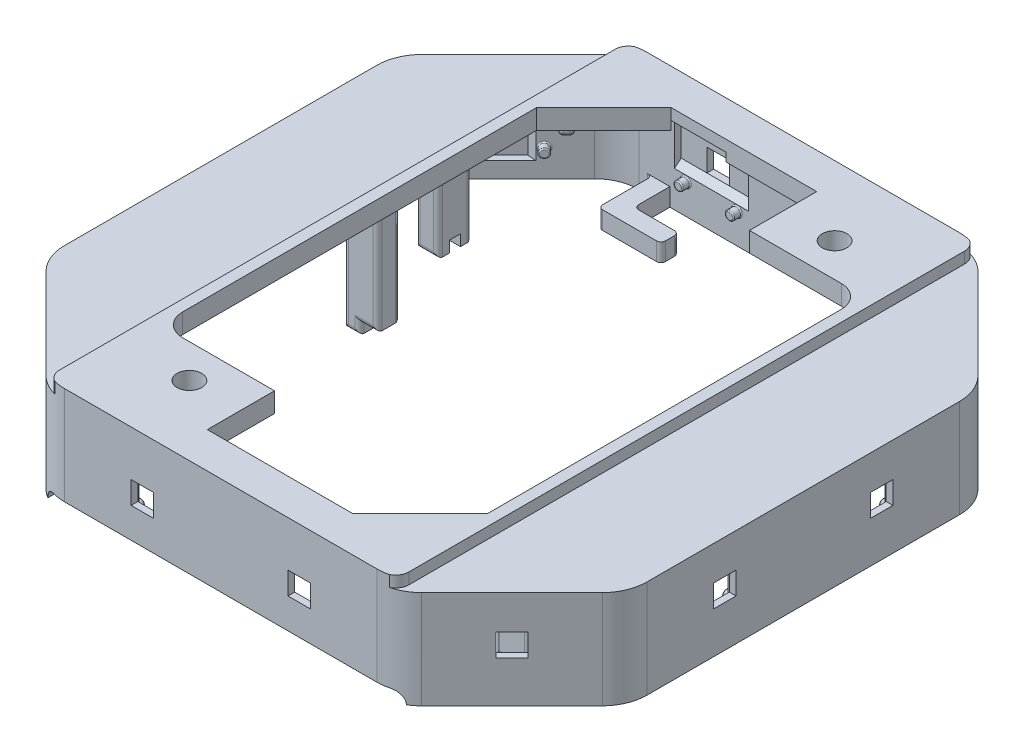
SolidWorks part; units mm, degrees
ref_plane "Front Plane" through (0, 0, 0) normal (0, 0, 1) x (1, 0, 0)
ref_plane "Top Plane" through (0, 0, 0) normal (0, 1, 0) x (1, 0, 0)
ref_plane "Right Plane" through (0, 0, 0) normal (1, 0, 0) x (0, 0, -1)
ref_axis "CenterAxis" through (0, 3.97, 0) along (0, -1, 0)
sketch "Sketch1" plane through (0, 0, 0) normal (0, 1, 0) x (1, 0, 0)
  line L0 (0, 34.664) -> (0, -51.0735) construction
  line L1 (-39, 65) -> (39, 65)
  line L2 (-39, 65) -> (-39, -65)
  line L3 (-39, -65) -> (39, -65)
  line L4 (39, 65) -> (39, -65)
  line L5 (-69.2084, 0) -> (81.5089, 0) construction
  dimension "D1" = 78
  dimension "D2" = 130
extrude "Boss-Extrude1" add sketch "Sketch1" along normal blind 2.5
sketch "Sketch4" plane through (0, 0, 0) normal (0, -1, 0) x (-1, 0, 0)
  line L1 (65, 65) -> (-65, 65)
  line L2 (65, 65) -> (65, -65)
  line L3 (65, -65) -> (-65, -65)
  line L4 (-65, 65) -> (-65, -65)
  line L6 (0, 118.1215) -> (0, -128.1726) construction
  line L7 (153.5171, 0) -> (-213.3352, 0) construction
  dimension "D1" = 130
  dimension "D2" = 130
extrude "Boss-Extrude2" add sketch "Sketch4" along normal blind 1.9
chamfer "Chamfer1" distance 26 angle 45 4 edges at (65, -0.95, 65) (-65, -0.95, 65) (-65, -0.95, -65) (65, -0.95, -65)
sketch "Sketch5" plane through (0, -1.9, 0) normal (0, -1, 0) x (-1, 0, 0)
  line L7 (39, 65) -> (-39, 65) construction
  line L9 (-39, 65) -> (-65, 39) construction
  line L10 (-65, 39) -> (-65, -39) construction
  line L11 (-65, -39) -> (-39, -65) construction
  line L12 (-39, -65) -> (39, -65) construction
  line L13 (39, -65) -> (65, -39) construction
  line L14 (65, -39) -> (65, 39) construction
  line L15 (65, 39) -> (39, 65) construction
  line L16 (39, 65) -> (-39, 65)
  line L17 (-39, 65) -> (-65, 39)
  line L18 (-65, 39) -> (-65, -39)
  line L19 (-65, -39) -> (-39, -65)
  line L20 (-39, -65) -> (39, -65)
  line L21 (39, -65) -> (65, -39)
  line L22 (65, -39) -> (65, 39)
  line L23 (65, 39) -> (39, 65)
  line L24 (37.7574, 62) -> (-37.7574, 62)
  line L25 (-37.7574, 62) -> (-62, 37.7574)
  line L26 (-62, 37.7574) -> (-62, -37.7574)
  line L27 (-62, -37.7574) -> (-37.7574, -62)
  line L28 (-37.7574, -62) -> (37.7574, -62)
  line L29 (37.7574, -62) -> (62, -37.7574)
  line L30 (62, -37.7574) -> (62, 37.7574)
  line L31 (62, 37.7574) -> (37.7574, 62)
  dimension "D1" = 3
extrude "Boss-Extrude3" add sketch "Sketch5" along normal blind 20
sketch "Sketch6" plane through (0, 0, 62) normal (0, 0, -1) x (-1, 0, 0)
  line L0 (0, -73.719) -> (0, 48.5048) construction
  line L1 (-15, -12.65) -> (-20, -12.65)
  line L2 (-15, -12.65) -> (-15, -7.65)
  line L3 (-15, -7.65) -> (-20, -7.65)
  line L4 (-20, -12.65) -> (-20, -7.65)
  line L5 (20, -12.65) -> (15, -12.65)
  line L6 (20, -12.65) -> (20, -7.65)
  line L7 (20, -7.65) -> (15, -7.65)
  line L8 (15, -12.65) -> (15, -7.65)
  line L10 (-37.7574, -1.9) -> (37.7574, -1.9) construction
  dimension "D1" = 5
  dimension "D2" = 5
  dimension "D3" = 5
  dimension "D4" = 5
  dimension "D5" = 30
  dimension "D6" = 5.75
  dimension "D7" = 5.75
extrude "Cut-Extrude3" cut sketch "Sketch6" against normal up to next
sketch "Sketch13" plane through (-49.8787, 0, 49.8787) normal (0.7071, 0, -0.7071) x (-0.7071, 0, -0.7071)
  line L0 (-17.1421, -1.9) -> (17.1421, -1.9) construction
  line L1 (2.5, -12.65) -> (-2.5, -12.65)
  line L2 (2.5, -12.65) -> (2.5, -7.65)
  line L3 (2.5, -7.65) -> (-2.5, -7.65)
  line L4 (-2.5, -12.65) -> (-2.5, -7.65)
  line L5 (0, -31.7169) -> (0, 9.0748) construction
  line L6 (-17.1421, -21.9) -> (-17.1421, -1.9) construction
  line L7 (17.1421, -21.9) -> (17.1421, -1.9) construction
  dimension "D1" = 5
  dimension "D2" = 5
  dimension "D3" = 5.75
extrude "Cut-Extrude6" cut sketch "Sketch13" against normal up to next
sketch "Sketch9" plane through (0, 0, 62) normal (0, 0, -1) x (-1, 0, 0)
  line L0 (39.1927, -10.15) -> (-34.1415, -10.15) construction
  line L4 (20, -18.4) -> (7.35, -18.4)
  line L5 (20, -18.4) -> (20, -1.9)
  line L6 (20, -1.9) -> (7.35, -1.9)
  line L7 (7.35, -18.4) -> (7.35, -1.9)
  line L10 (-20, -18.4) -> (-7.35, -18.4)
  line L11 (-20, -18.4) -> (-20, -1.9)
  line L12 (-20, -1.9) -> (-7.35, -1.9)
  line L13 (-7.35, -18.4) -> (-7.35, -1.9)
  line L18 (-37.7574, -1.9) -> (37.7574, -1.9) construction
  line L19 (20, -12.65) -> (20, -7.65) construction
  line L20 (-20, -7.65) -> (-20, -12.65) construction
  line L21 (20, -7.65) -> (15, -7.65) construction
  line L22 (15, -12.65) -> (20, -12.65) construction
  dimension "D1" = 12.65
  dimension "D2" = 12.65
extrude "Cut-Extrude5" cut sketch "Sketch9" against normal blind 1.5
sketch "Sketch14" plane through (-49.8787, 0, 49.8787) normal (0.7071, 0, -0.7071) x (-0.7071, 0, -0.7071)
  line L0 (-17.1421, -1.9) -> (17.1421, -1.9) construction
  line L1 (2.5, -1.9) -> (-10.15, -1.9)
  line L2 (2.5, -1.9) -> (2.5, -18.4)
  line L3 (2.5, -18.4) -> (-10.15, -18.4)
  line L4 (-10.15, -1.9) -> (-10.15, -18.4)
  line L5 (2.5, -12.65) -> (2.5, -7.65) construction
  line L6 (10.5909, -10.15) -> (-6.85, -10.15) construction
  line L7 (2.5, -7.65) -> (-2.5, -7.65) construction
  line L8 (-2.5, -12.65) -> (2.5, -12.65) construction
  dimension "D1" = 12.65
extrude "Cut-Extrude7" cut sketch "Sketch14" against normal blind 1.5
sketch "Sketch10" plane through (0, 0, 62) normal (0, 0, -1) x (-1, 0, 0)
  line L0 (45.2947, -10.154) -> (11.3128, -10.154) construction
  line L4 (7.35, -18.4) -> (5.35, -18.4)
  line L5 (7.35, -18.4) -> (7.35, -1.9)
  line L6 (7.35, -1.9) -> (5.35, -1.9)
  line L7 (5.35, -18.4) -> (5.35, -1.9)
  line L8 (-7.35, -1.9) -> (7.35, -1.9) construction
  line L9 (-7.35, -18.4) -> (-5.35, -18.4)
  line L10 (-7.35, -18.4) -> (-7.35, -1.9)
  line L11 (-7.35, -1.9) -> (-5.35, -1.9)
  line L12 (-5.35, -18.4) -> (-5.35, -1.9)
  circle A0 centre (22.59, -15.869) radius 1
  circle A1 centre (22.59, -4.439) radius 1
  circle A2 centre (-22.59, -15.869) radius 1
  circle A3 centre (-22.59, -4.439) radius 1
  dimension "D1" = 2
  dimension "D2" = 2
  dimension "D3" = 2
  dimension "D4" = 2
  dimension "D5" = 11.43
  dimension "D6" = 11.43
  dimension "D7" = 8.254
  dimension "D8" = 15.24
  dimension "D9" = 2
  dimension "D10" = 2
  dimension "D11" = 15.24
extrude "Boss-Extrude5" add sketch "Sketch10" along normal blind 1.75
sketch "Sketch15" plane through (-49.8787, 0, 49.8787) normal (0.7071, 0, -0.7071) x (-0.7071, 0, -0.7071)
  line L0 (-17.1421, -1.9) -> (-10.15, -1.9) construction
  line L1 (-10.15, -18.4) -> (-12.15, -18.4)
  line L2 (-10.15, -18.4) -> (-10.15, -1.9)
  line L3 (-10.15, -1.9) -> (-12.15, -1.9)
  line L4 (-12.15, -18.4) -> (-12.15, -1.9)
  line L5 (11.6969, -10.15) -> (-6.9983, -10.15) construction
  line L6 (-2.5, -12.65) -> (2.5, -12.65) construction
  line L7 (2.5, -7.65) -> (-2.5, -7.65) construction
  circle A0 centre (5.09, -15.865) radius 1
  circle A1 centre (5.09, -4.435) radius 1
  dimension "D2" = 2
  dimension "D3" = 2
  dimension "D1" = 2
  dimension "D4" = 15.24
  dimension "D5" = 11.43
extrude "Boss-Extrude9" add sketch "Sketch15" along normal blind 1.75
sketch "Sketch16" plane through (-62, 0, 0) normal (1, 0, 0) x (0, 0, -1)
  line L0 (0, -45.9705) -> (0, 131.7483) construction
  line L1 (20, -12.65) -> (15, -12.65)
  line L2 (20, -12.65) -> (20, -7.65)
  line L3 (20, -7.65) -> (15, -7.65)
  line L4 (15, -12.65) -> (15, -7.65)
  line L5 (-15, -12.65) -> (-20, -12.65)
  line L6 (-15, -12.65) -> (-15, -7.65)
  line L7 (-15, -7.65) -> (-20, -7.65)
  line L8 (-20, -12.65) -> (-20, -7.65)
  line L9 (37.7574, -21.9) -> (37.7574, -1.9) construction
  line L10 (-37.7574, -21.9) -> (-37.7574, -1.9) construction
  line L11 (-37.7574, -1.9) -> (37.7574, -1.9) construction
  dimension "D1" = 30
  dimension "D2" = 5
  dimension "D3" = 5
  dimension "D4" = 5
  dimension "D5" = 5
  dimension "D6" = 5.75
  dimension "D7" = 5.75
extrude "Cut-Extrude8" cut sketch "Sketch16" against normal up to next
sketch "Sketch17" plane through (-62, 0, 0) normal (1, 0, 0) x (0, 0, -1)
  line L0 (20, -12.65) -> (20, -7.65) construction
  line L1 (-15, -18.4) -> (-27.65, -18.4)
  line L2 (-15, -18.4) -> (-15, -1.9)
  line L3 (-15, -1.9) -> (-27.65, -1.9)
  line L4 (-27.65, -18.4) -> (-27.65, -1.9)
  line L5 (20, -18.4) -> (7.35, -18.4)
  line L6 (20, -18.4) -> (20, -1.9)
  line L7 (20, -1.9) -> (7.35, -1.9)
  line L8 (7.35, -18.4) -> (7.35, -1.9)
  line L9 (-37.7574, -1.9) -> (37.7574, -1.9) construction
  line L10 (-15, -12.65) -> (-15, -7.65) construction
  line L11 (27.4384, -10.15) -> (-34.0605, -10.15) construction
  line L12 (15, -12.65) -> (20, -12.65) construction
  line L13 (20, -7.65) -> (15, -7.65) construction
  dimension "D1" = 12.65
  dimension "D2" = 12.65
extrude "Cut-Extrude9" cut sketch "Sketch17" against normal blind 1.5
sketch "Sketch18" plane through (-62, 0, 0) normal (1, 0, 0) x (0, 0, -1)
  line L0 (32.9525, -10.15) -> (-38.3333, -10.15) construction
  line L1 (20, -12.65) -> (15, -12.65) construction
  line L2 (15, -7.65) -> (20, -7.65) construction
  line L3 (7.35, -1.9) -> (7.35, -18.4) construction
  line L4 (-27.65, -1.9) -> (-27.65, -18.4) construction
  line L5 (-15, -1.9) -> (7.35, -1.9) construction
  line L6 (7.35, -18.4) -> (5.35, -18.4)
  line L7 (7.35, -18.4) -> (7.35, -1.9)
  line L8 (7.35, -1.9) -> (5.35, -1.9)
  line L9 (5.35, -18.4) -> (5.35, -1.9)
  line L10 (-37.7574, -1.9) -> (-27.65, -1.9) construction
  line L11 (-27.65, -18.4) -> (-29.65, -18.4)
  line L12 (-27.65, -18.4) -> (-27.65, -1.9)
  line L13 (-27.65, -1.9) -> (-29.65, -1.9)
  line L14 (-29.65, -18.4) -> (-29.65, -1.9)
  circle A0 centre (22.59, -15.865) radius 1
  circle A1 centre (22.59, -4.435) radius 1
  circle A2 centre (-12.41, -15.865) radius 1
  circle A3 centre (-12.41, -4.435) radius 1
  dimension "D3" = 2
  dimension "D4" = 2
  dimension "D5" = 2
  dimension "D6" = 2
  dimension "D1" = 11.43
  dimension "D2" = 11.43
  dimension "D7" = 15.24
  dimension "D8" = 15.24
  dimension "D9" = 2
  dimension "D10" = 2
extrude "Boss-Extrude10" add sketch "Sketch18" along normal blind 1.75
sketch "Sketch19" plane through (49.8787, 0, 49.8787) normal (-0.7071, 0, -0.7071) x (-0.7071, 0, 0.7071)
  line L0 (0, -22.7201) -> (0, -10.1184) construction
  line L3 (17.1421, -21.9) -> (17.1421, -1.9) construction
  line L4 (-17.1421, -21.9) -> (-17.1421, -1.9) construction
  line L5 (-17.1421, -1.9) -> (17.1421, -1.9) construction
  line L6 (2.5, -12.65) -> (-2.5, -12.65)
  line L7 (2.5, -12.65) -> (2.5, -7.65)
  line L8 (2.5, -7.65) -> (-2.5, -7.65)
  line L9 (-2.5, -12.65) -> (-2.5, -7.65)
  dimension "D1" = 5
  dimension "D2" = 5
  dimension "D3" = 5.75
extrude "Cut-Extrude10" cut sketch "Sketch19" against normal up to next
sketch "Sketch20" plane through (49.8787, 0, 49.8787) normal (-0.7071, 0, -0.7071) x (-0.7071, 0, 0.7071)
  line L0 (-17.1421, -1.9) -> (17.1421, -1.9) construction
  line L1 (10.15, -18.4) -> (-2.5, -18.4)
  line L2 (10.15, -18.4) -> (10.15, -1.9)
  line L3 (10.15, -1.9) -> (-2.5, -1.9)
  line L4 (-2.5, -18.4) -> (-2.5, -1.9)
  line L5 (-2.5, -7.65) -> (-2.5, -12.65) construction
  line L6 (13.9228, -10.15) -> (-12.316, -10.15) construction
  line L7 (-2.5, -12.65) -> (2.5, -12.65) construction
  line L8 (2.5, -7.65) -> (-2.5, -7.65) construction
  dimension "D1" = 12.65
extrude "Cut-Extrude11" cut sketch "Sketch20" against normal blind 1.5
sketch "Sketch21" plane through (49.8787, 0, 49.8787) normal (-0.7071, 0, -0.7071) x (-0.7071, 0, 0.7071)
  line L0 (15.0556, -10.15) -> (-12.6108, -10.15) construction
  line L1 (12.15, -18.4) -> (10.15, -18.4)
  line L2 (12.15, -18.4) -> (12.15, -1.9)
  line L3 (12.15, -1.9) -> (10.15, -1.9)
  line L4 (10.15, -18.4) -> (10.15, -1.9)
  line L5 (2.5, -12.65) -> (-2.5, -12.65) construction
  line L6 (-2.5, -7.65) -> (2.5, -7.65) construction
  line L7 (10.15, -1.9) -> (17.1421, -1.9) construction
  circle A0 centre (-5.09, -15.865) radius 1
  circle A1 centre (-5.09, -4.435) radius 1
  dimension "D1" = 2
  dimension "D2" = 2
  dimension "D3" = 2
  dimension "D4" = 15.24
  dimension "D5" = 11.43
extrude "Boss-Extrude11" add sketch "Sketch21" along normal blind 1.75
sketch "Sketch22" plane through (62, 0, 0) normal (-1, 0, 0) x (0, 0, 1)
  line L0 (0, -48.3456) -> (0, 13.9543) construction
  line L1 (20, -12.65) -> (15, -12.65)
  line L2 (20, -12.65) -> (20, -7.65)
  line L3 (20, -7.65) -> (15, -7.65)
  line L4 (15, -12.65) -> (15, -7.65)
  line L5 (-15, -12.65) -> (-20, -12.65)
  line L6 (-15, -12.65) -> (-15, -7.65)
  line L7 (-15, -7.65) -> (-20, -7.65)
  line L8 (-20, -12.65) -> (-20, -7.65)
  line L9 (37.7574, -21.9) -> (37.7574, -1.9) construction
  line L10 (-37.7574, -21.9) -> (-37.7574, -1.9) construction
  line L12 (-37.7574, -1.9) -> (37.7574, -1.9) construction
  dimension "D1" = 5
  dimension "D2" = 5
  dimension "D3" = 5
  dimension "D4" = 5
  dimension "D5" = 5.75
  dimension "D6" = 5.75
  dimension "D7" = 30
extrude "Cut-Extrude12" cut sketch "Sketch22" against normal up to next
sketch "Sketch23" plane through (62, 0, 0) normal (-1, 0, 0) x (0, 0, 1)
  line L1 (27.65, -18.4) -> (15, -18.4)
  line L2 (27.65, -18.4) -> (27.65, -1.9)
  line L3 (27.65, -1.9) -> (15, -1.9)
  line L4 (15, -18.4) -> (15, -1.9)
  line L5 (-7.35, -18.4) -> (-20, -18.4)
  line L6 (-7.35, -18.4) -> (-7.35, -1.9)
  line L7 (-7.35, -1.9) -> (-20, -1.9)
  line L8 (-20, -18.4) -> (-20, -1.9)
  line L10 (-37.7574, -1.9) -> (37.7574, -1.9) construction
  line L11 (30.5276, -10.15) -> (-34.6722, -10.15) construction
  line L12 (20, -7.65) -> (15, -7.65) construction
  line L13 (15, -12.65) -> (20, -12.65) construction
  line L14 (15, -7.65) -> (15, -12.65) construction
  line L15 (-20, -7.65) -> (-20, -12.65) construction
  dimension "D1" = 12.65
  dimension "D2" = 12.65
extrude "Cut-Extrude13" cut sketch "Sketch23" against normal blind 1.5
sketch "Sketch24" plane through (62, 0, 0) normal (-1, 0, 0) x (0, 0, 1)
  line L0 (29.9106, -10.15) -> (-34.7522, -10.15) construction
  line L1 (29.65, -18.4) -> (27.65, -18.4)
  line L2 (29.65, -18.4) -> (29.65, -1.9)
  line L3 (29.65, -1.9) -> (27.65, -1.9)
  line L4 (27.65, -18.4) -> (27.65, -1.9)
  line L5 (-5.35, -18.4) -> (-7.35, -18.4)
  line L6 (-5.35, -18.4) -> (-5.35, -1.9)
  line L7 (-5.35, -1.9) -> (-7.35, -1.9)
  line L8 (-7.35, -18.4) -> (-7.35, -1.9)
  line L9 (20, -12.65) -> (15, -12.65) construction
  line L10 (15, -7.65) -> (20, -7.65) construction
  line L11 (-7.35, -1.9) -> (15, -1.9) construction
  line L12 (27.65, -1.9) -> (37.7574, -1.9) construction
  circle A0 centre (12.41, -15.865) radius 1
  circle A1 centre (12.41, -4.435) radius 1
  circle A2 centre (-22.59, -15.865) radius 1
  circle A3 centre (-22.59, -4.435) radius 1
  dimension "D1" = 2
  dimension "D2" = 2
  dimension "D3" = 2
  dimension "D4" = 2
  dimension "D5" = 2
  dimension "D6" = 2
  dimension "D7" = 15.24
  dimension "D8" = 15.24
  dimension "D9" = 11.43
  dimension "D10" = 11.43
extrude "Boss-Extrude12" add sketch "Sketch24" along normal blind 1.75
sketch "Sketch27" plane through (0, -1.9, 0) normal (0, -1, 0) x (-1, 0, 0)
  line L0 (-25.75, 57) -> (-9.25, 57)
  line L3 (37.7574, 62) -> (-37.7574, 62) construction
  line L4 (-9.25, 62) -> (-25.75, 62)
  line L5 (25.75, 62) -> (25.75, 57)
  line L6 (-9.25, 62) -> (-9.25, 57)
  line L7 (-25.75, 57) -> (-25.75, 62)
  line L8 (9.25, 62) -> (9.25, 57)
  line L9 (9.25, 57) -> (25.75, 57)
  line L10 (9.25, 62) -> (25.75, 62)
  line L11 (0, 103.5595) -> (0, 19.1897) construction
  dimension "D1" = 16.5
  dimension "D2" = 18.5
  dimension "D4" = 16.5
  dimension "D5" = 5
  dimension "D6" = 5
extrude "Cut-Extrude16" cut sketch "Sketch27" against normal up to surface (1.9 mm away) up to face at (-52, 0, -22.75)
sketch "Sketch32" plane through (0, 0, -62) normal (0, 0, 1) x (1, 0, 0)
  line L0 (0, -56.2842) -> (0, 5.1948) construction
  line L1 (20, -12.65) -> (15, -12.65)
  line L2 (20, -12.65) -> (20, -7.65)
  line L3 (20, -7.65) -> (15, -7.65)
  line L4 (15, -12.65) -> (15, -7.65)
  line L5 (-15, -12.65) -> (-20, -12.65)
  line L6 (-15, -12.65) -> (-15, -7.65)
  line L7 (-15, -7.65) -> (-20, -7.65)
  line L8 (-20, -12.65) -> (-20, -7.65)
  line L9 (-37.7574, -21.9) -> (-37.7574, -1.9) construction
  line L10 (37.7574, -21.9) -> (37.7574, -1.9) construction
  line L11 (-37.7574, 0) -> (37.7574, 0) construction
  dimension "D1" = 5
  dimension "D2" = 5
  dimension "D3" = 5
  dimension "D4" = 5
  dimension "D5" = 30
  dimension "D6" = 7.65
  dimension "D7" = 7.65
extrude "Cut-Extrude20" cut sketch "Sketch32" against normal up to next
sketch "Sketch33" plane through (0, 0, -62) normal (0, 0, 1) x (1, 0, 0)
  line L0 (15, -12.65) -> (20, -12.65) construction
  line L1 (25.75, -12.65) -> (9.25, -12.65)
  line L2 (25.75, -12.65) -> (25.75, 0)
  line L3 (25.75, 0) -> (9.25, 0)
  line L4 (9.25, -12.65) -> (9.25, 0)
  line L5 (17.5, -39.4676) -> (17.5, 3.7001) construction
  line L6 (-17.5, -41.1802) -> (-17.5, 6.7675) construction
  line L7 (15, -7.65) -> (15, -12.65) construction
  line L8 (20, -12.65) -> (20, -7.65) construction
  line L9 (-15, -12.65) -> (-15, -7.65) construction
  line L10 (-20, -7.65) -> (-20, -12.65) construction
  line L11 (-20, -12.65) -> (-15, -12.65) construction
  line L12 (-9.25, -12.65) -> (-25.75, -12.65)
  line L13 (-9.25, -12.65) -> (-9.25, 0)
  line L14 (-9.25, 0) -> (-25.75, 0)
  line L15 (-25.75, -12.65) -> (-25.75, 0)
  dimension "D1" = 12.65
  dimension "D2" = 16.5
  dimension "D3" = 12.65
  dimension "D4" = 16.5
extrude "Cut-Extrude21" cut sketch "Sketch33" against normal blind 1.5
sketch "Sketch34" plane through (0, 0, -62) normal (0, 0, 1) x (1, 0, 0)
  line L0 (17.5, 6.692) -> (17.5, -45.6178) construction
  line L1 (20, -7.65) -> (20, -12.65) construction
  line L2 (15, -12.65) -> (15, -7.65) construction
  line L4 (-17.5, -39.3596) -> (-17.5, 3.7236) construction
  line L5 (-15, -7.65) -> (-15, -12.65) construction
  line L6 (-20, -12.65) -> (-20, -7.65) construction
  line L10 (25.75, 0) -> (9.25, 0) construction
  line L11 (-9.25, 0) -> (-25.75, 0) construction
  circle A0 centre (23.215, -15.24) radius 1
  circle A1 centre (11.785, -15.24) radius 1
  circle A2 centre (-11.785, -15.24) radius 1
  circle A3 centre (-23.215, -15.24) radius 1
  dimension "D1" = 2
  dimension "D2" = 2
  dimension "D5" = 2
  dimension "D6" = 2
  dimension "D3" = 11.43
  dimension "D4" = 15.24
  dimension "D7" = 11.43
  dimension "D8" = 15.24
extrude "Boss-Extrude14" add sketch "Sketch34" along normal blind 1.75
sketch "Sketch35" plane through (49.8787, 0, -49.8787) normal (-0.7071, 0, 0.7071) x (0.7071, 0, 0.7071)
  line L0 (-17.1421, -1.9) -> (17.1421, -1.9) construction
  line L1 (2.5, -12.65) -> (-2.5, -12.65)
  line L2 (2.5, -12.65) -> (2.5, -7.65)
  line L3 (2.5, -7.65) -> (-2.5, -7.65)
  line L4 (-2.5, -12.65) -> (-2.5, -7.65)
  line L5 (0, -41.1131) -> (0, 9.0774) construction
  line L6 (17.1421, -21.9) -> (17.1421, -1.9) construction
  line L7 (-17.1421, -21.9) -> (-17.1421, -1.9) construction
  dimension "D1" = 5
  dimension "D2" = 5
  dimension "D3" = 5.75
extrude "Cut-Extrude22" cut sketch "Sketch35" against normal up to next
sketch "Sketch36" plane through (49.8787, 0, -49.8787) normal (-0.7071, 0, 0.7071) x (0.7071, 0, 0.7071)
  line L0 (-2.5, -7.65) -> (-2.5, -12.65) construction
  line L1 (10.15, -1.9) -> (-2.5, -1.9)
  line L2 (10.15, -1.9) -> (10.15, -18.4)
  line L3 (10.15, -18.4) -> (-2.5, -18.4)
  line L4 (-2.5, -1.9) -> (-2.5, -18.4)
  line L5 (14.9901, -10.15) -> (-10.7496, -10.15) construction
  line L6 (-2.5, -12.65) -> (2.5, -12.65) construction
  line L7 (2.5, -7.65) -> (-2.5, -7.65) construction
  line L8 (-17.1421, -1.9) -> (17.1421, -1.9) construction
  dimension "D1" = 12.65
extrude "Cut-Extrude23" cut sketch "Sketch36" against normal blind 1.5
sketch "Sketch37" plane through (49.8787, 0, -49.8787) normal (-0.7071, 0, 0.7071) x (0.7071, 0, 0.7071)
  line L0 (10.15, -1.9) -> (17.1421, -1.9) construction
  line L1 (10.15, -18.4) -> (12.15, -18.4)
  line L2 (10.15, -18.4) -> (10.15, -1.9)
  line L3 (10.15, -1.9) -> (12.15, -1.9)
  line L4 (12.15, -18.4) -> (12.15, -1.9)
  line L5 (15.4954, -10.15) -> (-15.257, -10.15) construction
  line L6 (2.5, -7.65) -> (-2.5, -7.65) construction
  line L7 (-2.5, -12.65) -> (2.5, -12.65) construction
  circle A0 centre (-5.09, -15.865) radius 1
  circle A1 centre (-5.09, -4.435) radius 1
  dimension "D2" = 2
  dimension "D3" = 2
  dimension "D1" = 2
  dimension "D4" = 11.43
  dimension "D5" = 15.24
extrude "Boss-Extrude15" add sketch "Sketch37" along normal blind 1.75
fillet "Fillet5" radius 3 4 edges tangent propagation no
sketch "Sketch38" plane through (-49.8787, 0, -49.8787) normal (0.7071, 0, 0.7071) x (0.7071, 0, -0.7071)
  line L0 (0, -45.2412) -> (0, 20.7133) construction
  line L1 (-17.1421, -21.9) -> (-17.1421, -1.9) construction
  line L2 (17.1421, -21.9) -> (17.1421, -1.9) construction
  line L3 (-17.1421, -1.9) -> (17.1421, -1.9) construction
  line L4 (2.5, -12.65) -> (-2.5, -12.65)
  line L5 (2.5, -12.65) -> (2.5, -7.65)
  line L6 (2.5, -7.65) -> (-2.5, -7.65)
  line L7 (-2.5, -12.65) -> (-2.5, -7.65)
  dimension "D1" = 5
  dimension "D2" = 5
  dimension "D3" = 5.75
extrude "Cut-Extrude24" cut sketch "Sketch38" against normal up to next contours L6 L7 L4 L5
sketch "Sketch39" plane through (-49.8787, 0, -49.8787) normal (0.7071, 0, 0.7071) x (0.7071, 0, -0.7071)
  line L0 (2.5, -12.65) -> (2.5, -7.65) construction
  line L1 (2.5, -18.4) -> (-10.15, -18.4)
  line L2 (2.5, -18.4) -> (2.5, -1.9)
  line L3 (2.5, -1.9) -> (-10.15, -1.9)
  line L4 (-10.15, -18.4) -> (-10.15, -1.9)
  line L5 (-17.1421, -1.9) -> (17.1421, -1.9) construction
  line L6 (7.9642, -10.15) -> (-14.3354, -10.15) construction
  line L7 (2.5, -7.65) -> (-2.5, -7.65) construction
  line L8 (2.5, -12.65) -> (-2.5, -12.65) construction
  dimension "D1" = 12.65
extrude "Cut-Extrude25" cut sketch "Sketch39" against normal blind 1.5
sketch "Sketch40" plane through (-49.8787, 0, -49.8787) normal (0.7071, 0, 0.7071) x (0.7071, 0, -0.7071)
  line L0 (-17.1421, -1.9) -> (-10.15, -1.9) construction
  line L1 (-10.15, -18.4) -> (-12.15, -18.4)
  line L2 (-10.15, -18.4) -> (-10.15, -1.9)
  line L3 (-10.15, -1.9) -> (-12.15, -1.9)
  line L4 (-12.15, -18.4) -> (-12.15, -1.9)
  line L5 (11.3212, -10.15) -> (-14.9762, -10.15) construction
  line L6 (-2.5, -12.65) -> (2.5, -12.65) construction
  line L7 (-2.5, -7.65) -> (2.5, -7.65) construction
  circle A0 centre (5.09, -15.865) radius 1
  circle A1 centre (5.09, -4.435) radius 1
  dimension "D2" = 2
  dimension "D3" = 2
  dimension "D1" = 2
  dimension "D4" = 11.43
  dimension "D5" = 15.24
extrude "Boss-Extrude16" add sketch "Sketch40" along normal blind 1.75
fillet "Fillet6" radius 10 16 edges at (-65, -10.95, -39) (65, -10.95, -39) (65, -10.95, 39) (-65, -10.95, 39) (-37.7574, -11.9, -62) (-62, -11.9, -37.7574) (-62, -11.9, 37.7574) (-37.7574, -11.9, 62) (37.7574, -11.9, 62) (62, -11.9, 37.7574) (62, -11.9, -37.7574) (37.7574, -11.9, -62)
sketch "Sketch41" plane through (0, -1.9, 0) normal (0, -1, 0) x (-1, 0, 0)
  line L0 (-49.9494, -39.5549) -> (-51.7172, -37.7872)
  line L1 (-51.7172, -37.7872) -> (-49.9494, -36.0194)
  line L2 (-49.9494, -36.0194) -> (-48.1816, -37.7872)
  line L3 (-48.1816, -37.7872) -> (-49.9494, -39.5549)
  line L4 (-43.7622, -58.1165) -> (-41.4641, -55.8184) construction
  line L5 (-40.0499, -57.2326) -> (-41.4641, -55.8184) construction
  line L6 (37.7872, 51.7172) -> (39.5549, 49.9494)
  line L7 (-27.35, -52.25) -> (-24.85, -52.25)
  line L8 (-27.35, -52.25) -> (-27.35, -54.75)
  line L9 (-27.35, -54.75) -> (-24.85, -54.75)
  line L10 (-24.85, -52.25) -> (-24.85, -54.75)
  line L11 (24.85, -52.25) -> (27.35, -52.25)
  line L12 (24.85, -52.25) -> (24.85, -54.75)
  line L13 (24.85, -54.75) -> (27.35, -54.75)
  line L14 (27.35, -52.25) -> (27.35, -54.75)
  line L15 (52.25, -7.65) -> (54.75, -7.65)
  line L16 (52.25, -7.65) -> (52.25, -10.15)
  line L17 (52.25, -10.15) -> (54.75, -10.15)
  line L18 (54.75, -7.65) -> (54.75, -10.15)
  line L19 (52.25, 27.35) -> (54.75, 27.35)
  line L20 (52.25, 27.35) -> (52.25, 24.85)
  line L21 (52.25, 24.85) -> (54.75, 24.85)
  line L22 (54.75, 27.35) -> (54.75, 24.85)
  line L23 (-54.75, -7.65) -> (-52.25, -7.65)
  line L24 (-54.75, -7.65) -> (-54.75, -10.15)
  line L25 (-54.75, -10.15) -> (-52.25, -10.15)
  line L26 (-52.25, -7.65) -> (-52.25, -10.15)
  line L27 (-54.75, 27.35) -> (-52.25, 27.35)
  line L28 (-54.75, 27.35) -> (-54.75, 24.85)
  line L29 (-54.75, 24.85) -> (-52.25, 24.85)
  line L30 (-52.25, 27.35) -> (-52.25, 24.85)
  line L31 (39.5549, 49.9494) -> (37.7872, 48.1816)
  line L32 (37.7872, 48.1816) -> (36.0194, 49.9494)
  line L33 (36.0194, 49.9494) -> (37.7872, 51.7172)
  line L34 (-39.5549, 49.9494) -> (-37.7872, 48.1816)
  line L35 (-37.7872, 48.1816) -> (-36.0194, 49.9494)
  line L36 (-36.0194, 49.9494) -> (-37.7872, 51.7172)
  line L37 (-37.7872, 51.7172) -> (-39.5549, 49.9494)
  line L38 (-5.35, -60.25) -> (-7.35, -60.25) construction
  line L39 (-7.35, -63.5) -> (-7.35, -60.25) construction
  line L40 (7.35, -60.25) -> (7.35, -62) construction
  line L41 (5.35, -60.25) -> (7.35, -60.25) construction
  line L42 (51.7172, -37.7872) -> (49.9494, -39.5549)
  line L43 (49.9494, -39.5549) -> (48.1816, -37.7872)
  line L44 (48.1816, -37.7872) -> (49.9494, -36.0194)
  line L45 (49.9494, -36.0194) -> (51.7172, -37.7872)
  line L48 (41.4641, -55.8184) -> (40.0499, -57.2326) construction
  line L49 (43.7622, -58.1165) -> (41.4641, -55.8184) construction
  line L50 (-60.25, -27.65) -> (-62, -27.65) construction
  line L51 (-60.25, -29.65) -> (-60.25, -27.65) construction
  line L52 (-60.25, 7.35) -> (-62, 7.35) construction
  line L53 (-60.25, 5.35) -> (-60.25, 7.35) construction
  line L54 (-58.1165, 43.7622) -> (-55.8184, 41.4641) construction
  line L55 (-57.2326, 40.0499) -> (-55.8184, 41.4641) construction
  line L56 (-55.8184, 41.4641) -> (-57.0558, 42.7015) construction
  line L57 (-55.8184, 41.4641) -> (-57.2326, 40.0499) construction
  line L58 (60.25, -27.65) -> (62, -27.65) construction
  line L59 (60.25, -29.65) -> (60.25, -27.65) construction
  line L60 (60.25, 7.35) -> (62, 7.35) construction
  line L61 (60.25, 5.35) -> (60.25, 7.35) construction
  line L64 (58.1165, 43.7622) -> (55.8184, 41.4641) construction
  line L65 (57.2326, 40.0499) -> (55.8184, 41.4641) construction
  dimension "D1" = 17.5
  dimension "D2" = 5.5
  dimension "D3" = 2.5
  dimension "D4" = 2.5
  dimension "D5" = 5.5
  dimension "D6" = 17.5
  dimension "D7" = 2.5
  dimension "D8" = 2.5
  dimension "D9" = 17.5
  dimension "D10" = 5.5
  dimension "D11" = 2.5
  dimension "D12" = 2.5
  dimension "D13" = 5.5
  dimension "D14" = 17.5
  dimension "D15" = 2.5
  dimension "D16" = 2.5
  dimension "D17" = 17.5
  dimension "D18" = 5.5
  dimension "D19" = 2.5
  dimension "D20" = 2.5
  dimension "D21" = 17.5
  dimension "D22" = 5.5
  dimension "D23" = 2.5
  dimension "D24" = 2.5
  dimension "D25" = 17.5
  dimension "D26" = 5.5
  dimension "D27" = 2.5
  dimension "D28" = 2.5
  dimension "D29" = 17.5
  dimension "D30" = 5.5
  dimension "D31" = 2.5
  dimension "D32" = 2.5
  dimension "D33" = 17.5
  dimension "D34" = 5.5
  dimension "D35" = 2.5
  dimension "D36" = 2.5
  dimension "D37" = 17.5
  dimension "D38" = 5.5
  dimension "D39" = 2.5
  dimension "D40" = 2.5
extrude "Boss-Extrude17" add sketch "Sketch41" along normal blind 5
sketch "Sketch42" plane through (0, 0, -62) normal (0, 0, 1) x (1, 0, 0)
  line L0 (25.75, -12.65) -> (25.75, -1.9) construction
  line L1 (30.75, -21.9) -> (26.75, -21.9)
  line L2 (30.75, -21.9) -> (30.75, -17.9)
  line L3 (30.75, -17.9) -> (26.75, -17.9)
  line L4 (26.75, -21.9) -> (26.75, -17.9)
  line L5 (-26.75, -21.9) -> (-30.75, -21.9)
  line L6 (-26.75, -21.9) -> (-26.75, -17.9)
  line L7 (-26.75, -17.9) -> (-30.75, -17.9)
  line L8 (-30.75, -21.9) -> (-30.75, -17.9)
  line L10 (-25.75, -1.9) -> (-25.75, -12.65) construction
  line L12 (-9.25, 0) -> (-25.75, 0) construction
  line L13 (25.75, 0) -> (9.25, 0) construction
  dimension "D1" = 4
  dimension "D2" = 4
  dimension "D3" = 4
  dimension "D4" = 4
  dimension "D5" = 1
  dimension "D6" = 17.9
  dimension "D7" = 1
  dimension "D8" = 17.9
extrude "Boss-Extrude18" add sketch "Sketch42" along normal blind 12
sketch "Sketch43" plane through (26.75, 0, 0) normal (-1, 0, 0) x (0, 0, 1)
  line L0 (-50, -17.9) -> (-62, -17.9) construction
  line L1 (-50, -21.9) -> (-54, -21.9)
  line L2 (-50, -21.9) -> (-50, -17.9)
  line L3 (-50, -17.9) -> (-54, -17.9)
  line L4 (-54, -21.9) -> (-54, -17.9)
  dimension "D1" = 4
extrude "Boss-Extrude19" add sketch "Sketch43" along normal blind 10
sketch "Sketch44" plane through (-26.75, 0, 0) normal (1, 0, 0) x (0, 0, -1)
  line L0 (50, -17.9) -> (62, -17.9) construction
  line L1 (50, -21.9) -> (54, -21.9)
  line L2 (50, -21.9) -> (50, -17.9)
  line L3 (50, -17.9) -> (54, -17.9)
  line L4 (54, -21.9) -> (54, -17.9)
  dimension "D1" = 4
extrude "Boss-Extrude20" add sketch "Sketch44" along normal blind 10
fillet "Fillet8" radius 0.75 120 edges at (54.75, -6.9, -26.1) (54.75, -1.9, -26.1) (54.75, -4.4, -24.85) (53.5, -6.9, -24.85) (53.5, -1.9, -24.85) (52.25, -4.4, -24.85) (52.25, -6.9, -26.1) (52.25, -1.9, -26.1) (52.25, -4.4, -27.35) (53.5, -6.9, -27.35) (54.75, -4.4, -27.35) (53.5, -1.9, -27.35) (38.671, -6.9, -50.8333) (38.671, -1.9, -50.8333) (39.5549, -4.4, -49.9494) (38.671, -6.9, -49.0655) (38.671, -1.9, -49.0655) (37.7872, -4.4, -48.1816) (36.9033, -6.9, -49.0655) (36.9033, -1.9, -49.0655) (36.0194, -4.4, -49.9494) (36.9033, -6.9, -50.8333) (37.7872, -4.4, -51.7172) (36.9033, -1.9, -50.8333) (-38.671, -6.9, -50.8333) (-38.671, -1.9, -50.8333) (-37.7872, -4.4, -51.7172) (-36.9033, -6.9, -50.8333) (-36.9033, -1.9, -50.8333) (-36.0194, -4.4, -49.9494) (-36.9033, -6.9, -49.0655) (-36.9033, -1.9, -49.0655) (-37.7872, -4.4, -48.1816) (-38.671, -6.9, -49.0655) (-39.5549, -4.4, -49.9494) (-38.671, -1.9, -49.0655) (-54.75, -6.9, -26.1) (-54.75, -1.9, -26.1) (-54.75, -4.4, -27.35) (-53.5, -6.9, -27.35) (-53.5, -1.9, -27.35) (-53.5, -6.9, -24.85) (-54.75, -4.4, -24.85) (-53.5, -1.9, -24.85) (-52.25, -4.4, -27.35) (-52.25, -6.9, -26.1) (-52.25, -4.4, -24.85) (-52.25, -1.9, -26.1) (-54.75, -6.9, 8.9) (-54.75, -1.9, 8.9) (-53.5, -6.9, 10.15) (-54.75, -4.4, 10.15) (-53.5, -1.9, 10.15) (-54.75, -4.4, 7.65) (-53.5, -6.9, 7.65) (-53.5, -1.9, 7.65) (-52.25, -4.4, 7.65) (-52.25, -6.9, 8.9) (-52.25, -4.4, 10.15) (-52.25, -1.9, 8.9) (-49.0655, -6.9, 36.9033) (-49.0655, -1.9, 36.9033) (-50.8333, -6.9, 36.9033) (-49.9494, -4.4, 36.0194) (-50.8333, -1.9, 36.9033) (-50.8333, -6.9, 38.671) (-51.7172, -4.4, 37.7872) (-50.8333, -1.9, 38.671) (-48.1816, -4.4, 37.7872) (-49.0655, -6.9, 38.671) (-49.9494, -4.4, 39.5549) (-49.0655, -1.9, 38.671) (-26.1, -6.9, 54.75) (-26.1, -1.9, 54.75) (-27.35, -4.4, 54.75) (-27.35, -6.9, 53.5) (-27.35, -1.9, 53.5) (-27.35, -4.4, 52.25) (-26.1, -6.9, 52.25) (-26.1, -1.9, 52.25) (-24.85, -4.4, 52.25) (-24.85, -6.9, 53.5) (-24.85, -4.4, 54.75) (-24.85, -1.9, 53.5) (26.1, -6.9, 52.25) (26.1, -1.9, 52.25) (24.85, -6.9, 53.5) (24.85, -4.4, 52.25) (24.85, -1.9, 53.5) (26.1, -6.9, 54.75) (24.85, -4.4, 54.75) (26.1, -1.9, 54.75) (27.35, -4.4, 52.25) (27.35, -6.9, 53.5) (27.35, -4.4, 54.75) (27.35, -1.9, 53.5) (53.5, -6.9, 10.15) (53.5, -1.9, 10.15) (52.25, -4.4, 10.15) (52.25, -6.9, 8.9) (52.25, -1.9, 8.9) (52.25, -4.4, 7.65) (53.5, -6.9, 7.65) (53.5, -1.9, 7.65) (54.75, -4.4, 7.65) (54.75, -6.9, 8.9) (54.75, -4.4, 10.15) (54.75, -1.9, 8.9) (50.8333, -6.9, 38.671) (50.8333, -1.9, 38.671) (49.9494, -4.4, 39.5549) (49.0655, -6.9, 38.671) (49.0655, -1.9, 38.671) (48.1816, -4.4, 37.7872) (49.0655, -6.9, 36.9033) (49.0655, -1.9, 36.9033) (49.9494, -4.4, 36.0194) (50.8333, -6.9, 36.9033) (51.7172, -4.4, 37.7872) (50.8333, -1.9, 36.9033)
sketch "Sketch47" plane through (0, -1.9, 0) normal (0, -1, 0) x (-1, 0, 0)
  circle A1 centre (-22.5, 49.5) radius 2.75
  circle A3 centre (22.5, -49.5) radius 2.75
  dimension "D3" = 5.5
  dimension "D6" = 5.5
  dimension "D1" = 22.5
  dimension "D2" = 49.5
  dimension "D4" = 49.5
  dimension "D5" = 22.5
extrude "Cut-Extrude28" cut sketch "Sketch47" against normal through all
sketch "Sketch48" plane through (0, -1.9, 0) normal (0, -1, 0) x (-1, 0, 0)
  line L1 (-45, 12.5) -> (-37.5, 12.5)
  line L2 (-45, 12.5) -> (-45, 7.5)
  line L3 (-45, 7.5) -> (-37.5, 7.5)
  line L4 (-37.5, 12.5) -> (-37.5, 7.5)
  line L5 (37.5, 12.5) -> (45, 12.5)
  line L6 (37.5, 12.5) -> (37.5, 7.5)
  line L7 (37.5, 7.5) -> (45, 7.5)
  line L8 (45, 12.5) -> (45, 7.5)
  line L9 (-45, -36.25) -> (-37.5, -36.25)
  line L10 (-45, -36.25) -> (-45, -41.25)
  line L11 (-45, -41.25) -> (-37.5, -41.25)
  line L12 (-37.5, -36.25) -> (-37.5, -41.25)
  line L13 (37.5, -36.25) -> (45, -36.25)
  line L14 (37.5, -36.25) -> (37.5, -41.25)
  line L15 (37.5, -41.25) -> (45, -41.25)
  line L16 (45, -36.25) -> (45, -41.25)
  dimension "D1" = 7.5
  dimension "D2" = 5
  dimension "D3" = 7.5
  dimension "D4" = 5
  dimension "D5" = 7.5
  dimension "D6" = 5
  dimension "D7" = 7.5
  dimension "D8" = 5
  dimension "D9" = 36.25
  dimension "D10" = 37.5
  dimension "D11" = 36.25
  dimension "D12" = 37.5
  dimension "D13" = 7.5
  dimension "D14" = 37.5
  dimension "D15" = 37.5
  dimension "D16" = 7.5
extrude "Boss-Extrude21" add sketch "Sketch48" along normal blind 25
sketch "Sketch49" plane through (0, -26.9, 0) normal (0, -1, 0) x (-1, 0, 0)
  line L0 (37.5, -41.25) -> (45, -41.25) construction
  line L1 (37.5, -36.25) -> (41.5, -36.25)
  line L2 (37.5, -36.25) -> (37.5, -41.25)
  line L3 (37.5, -41.25) -> (41.5, -41.25)
  line L4 (41.5, -36.25) -> (41.5, -41.25)
  line L5 (-45, -41.25) -> (-37.5, -41.25) construction
  line L6 (-37.5, -36.25) -> (-41.5, -36.25)
  line L7 (-37.5, -36.25) -> (-37.5, -41.25)
  line L8 (-37.5, -41.25) -> (-41.5, -41.25)
  line L9 (-41.5, -36.25) -> (-41.5, -41.25)
  line L10 (37.5, 7.5) -> (45, 7.5) construction
  line L11 (37.5, 12.5) -> (41.5, 12.5)
  line L12 (37.5, 12.5) -> (37.5, 7.5)
  line L13 (37.5, 7.5) -> (41.5, 7.5)
  line L14 (41.5, 12.5) -> (41.5, 7.5)
  line L15 (-45, 7.5) -> (-37.5, 7.5) construction
  line L16 (-37.5, 12.5) -> (-41.5, 12.5)
  line L17 (-37.5, 12.5) -> (-37.5, 7.5)
  line L18 (-37.5, 7.5) -> (-41.5, 7.5)
  line L19 (-41.5, 12.5) -> (-41.5, 7.5)
  dimension "D1" = 4
  dimension "D2" = 4
  dimension "D3" = 4
  dimension "D4" = 4
extrude "Cut-Extrude29" cut sketch "Sketch49" against normal blind 2.5
sketch "Sketch50" plane through (0, -1.9, 0) normal (0, -1, 0) x (-1, 0, 0)
  line L1 (45, 23.5) -> (40, 23.5)
  line L2 (45, 23.5) -> (45, 31)
  line L3 (45, 31) -> (40, 31)
  line L4 (40, 23.5) -> (40, 31)
  line L5 (-40, 23.5) -> (-45, 23.5)
  line L6 (-40, 23.5) -> (-40, 31)
  line L7 (-40, 31) -> (-45, 31)
  line L8 (-45, 23.5) -> (-45, 31)
  dimension "D1" = 40
  dimension "D2" = 23.5
  dimension "D3" = 23.5
  dimension "D4" = 40
  dimension "D5" = 7.5
  dimension "D6" = 7.5
  dimension "D7" = 5
  dimension "D8" = 5
extrude "Boss-Extrude22" add sketch "Sketch50" along normal blind 17.5
sketch "Sketch51" plane through (0, -19.4, 0) normal (0, -1, 0) x (1, 0, 0)
  line L0 (-45, -23.5) -> (-45, -31) construction
  line L1 (-45, -26) -> (-40, -26)
  line L2 (-45, -26) -> (-45, -28.5)
  line L3 (-45, -28.5) -> (-40, -28.5)
  line L4 (-40, -26) -> (-40, -28.5)
  line L5 (-40, -31) -> (-40, -23.5) construction
  line L6 (-40, -23.5) -> (-45, -23.5) construction
  line L7 (-45, -31) -> (-40, -31) construction
  line L8 (40, -23.5) -> (40, -31) construction
  line L9 (40, -26) -> (45, -26)
  line L10 (40, -26) -> (40, -28.5)
  line L11 (40, -28.5) -> (45, -28.5)
  line L12 (45, -26) -> (45, -28.5)
  line L13 (45, -31) -> (45, -23.5) construction
  line L14 (45, -23.5) -> (40, -23.5) construction
  line L15 (40, -31) -> (45, -31) construction
  dimension "D1" = 2.5
  dimension "D2" = 2.5
  dimension "D3" = 2.5
  dimension "D4" = 2.5
extrude "Cut-Extrude30" cut sketch "Sketch51" against normal blind 2.5
sketch "Sketch52" plane through (0, -1.9, 0) normal (0, -1, 0) x (-1, 0, 0)
  line L0 (-36.5, 42) -> (-11, 42)
  line L1 (-11, 42) -> (-11, 57)
  line L2 (36.5, 42) -> (36.5, -42)
  line L3 (-11, 57) -> (21.5, 57)
  line L4 (-36.5, 42) -> (-36.5, -42)
  line L5 (36.5, -42) -> (11, -42)
  line L6 (11, -42) -> (11, -57)
  line L7 (-21.5, -57) -> (11, -57)
  line L10 (0, 85.3161) -> (0, -75.731) construction
  line L11 (-86.6512, 0) -> (132.8598, 0) construction
  line L12 (21.5, 57) -> (36.5, 42)
  line L13 (-36.5, -42) -> (-21.5, -57)
  circle A1 centre (22.5, -49.5) radius 2.75 construction
  circle A2 centre (-22.5, 49.5) radius 2.75 construction
  point P0 (0, 0)
  dimension "D2" = 7.5
  dimension "D3" = 11.5
  dimension "D4" = 11.5
  dimension "D5" = 7.5
  dimension "D1" = 15
  dimension "D6" = 15
  dimension "D7" = 15
  dimension "D8" = 15
  dimension "D9" = 114
  dimension "D10" = 73
extrude "Cut-Extrude32" cut sketch "Sketch52" against normal blind 10
fillet "Fillet10" radius 5 2 edges at (-36.5, 0.3, 42) (36.5, 0.3, -42)
fillet "Fillet11" radius 1 11 edges at (-26.75, -19.9, -54) (-16.75, -19.9, -54) (-16.75, -19.9, -50) (-30.75, -19.9, -50) (-30.75, -19.9, -62) (30.75, -19.9, -62) (30.75, -19.9, -50) (16.75, -19.9, -50) (16.75, -19.9, -54) (26.75, -19.9, -54) (26.75, -19.9, -62)
sketch "Sketch53" plane through (0, 0, 65) normal (0, 0, 1) x (1, 0, 0)
  line L0 (-37.5, -19.4) -> (37.5, -19.4)
  line L1 (-40, -21.9) -> (40, -21.9)
  line L2 (0, 30.1492) -> (0, -103.2761) construction
  line L3 (34.8579, -21.9) -> (-34.8579, -21.9) construction
  arc A0 (-40, -21.9) -> (-37.5, -19.4) centre (-37.5, -21.9) cw
  arc A1 (37.5, -19.4) -> (40, -21.9) centre (37.5, -21.9) cw
  dimension "D1" = 2.5
  dimension "D2" = 2.5
  dimension "D3" = 2.5
  dimension "D4" = 80
extrude "Cut-Extrude33" cut sketch "Sketch53" against normal up to next
fillet "Fillet12" radius 1 76 edges at (-41.25, -1.9, 36.25) (-45, -1.9, 38.75) (-41.25, -1.9, 41.25) (-37.5, -1.9, 38.75) (-41.25, -1.9, -7.5) (-37.5, -1.9, -10) (-41.25, -1.9, -12.5) (-45, -1.9, -10) (-42.5, -1.9, -31) (-45, -1.9, -27.25) (-42.5, -1.9, -23.5) (-40, -1.9, -27.25) (42.5, -1.9, -23.5) (45, -1.9, -27.25) (42.5, -1.9, -31) (40, -1.9, -27.25) (41.25, -1.9, -7.5) (37.5, -1.9, -10) (41.25, -1.9, -12.5) (45, -1.9, -10) (45, -1.9, 38.75) (41.25, -1.9, 36.25) (41.25, -1.9, 41.25) (37.5, -1.9, 38.75) (-45, -10.65, -31) (-42.5, -19.4, -31) (-40, -10.65, -31) (-40, -10.65, -23.5) (-42.5, -19.4, -23.5) (-45, -10.65, -23.5) (45, -10.65, -23.5) (42.5, -19.4, -23.5) (40, -10.65, -23.5) (40, -10.65, -31) (42.5, -19.4, -31) (45, -10.65, -31) (37.5, -13.15, 41.25) (45, -14.4, 41.25) (43.25, -26.9, 41.25) (41.5, -25.65, 41.25) (39.5, -24.4, 41.25) (45, -14.4, 36.25) (37.5, -13.15, 36.25) (39.5, -24.4, 36.25) (41.5, -25.65, 36.25) (43.25, -26.9, 36.25) (37.5, -13.15, -7.5) (45, -14.4, -7.5) (43.25, -26.9, -7.5) (41.5, -25.65, -7.5) (39.5, -24.4, -7.5) (45, -14.4, -12.5) (37.5, -13.15, -12.5) (39.5, -24.4, -12.5) (41.5, -25.65, -12.5) (43.25, -26.9, -12.5) (-37.5, -13.15, 36.25) (-45, -14.4, 36.25) (-43.25, -26.9, 36.25) (-41.5, -25.65, 36.25) (-39.5, -24.4, 36.25) (-45, -14.4, 41.25) (-37.5, -13.15, 41.25) (-39.5, -24.4, 41.25) (-41.5, -25.65, 41.25) (-43.25, -26.9, 41.25) (-45, -14.4, -7.5) (-37.5, -13.15, -7.5) (-39.5, -24.4, -7.5) (-41.5, -25.65, -7.5) (-43.25, -26.9, -7.5) (-37.5, -13.15, -12.5) (-45, -14.4, -12.5) (-43.25, -26.9, -12.5) (-41.5, -25.65, -12.5) (-39.5, -24.4, -12.5)
fillet "Fillet13" radius 0.25 48 edges at (-54.185, -4.435, 45.5724) (-52.9475, -4.435, 44.335) (-54.185, -15.865, 45.5724) (-52.9475, -15.865, 44.335) (-62, -15.865, 11.41) (-60.25, -15.865, 11.41) (-62, -4.435, 11.41) (-60.25, -4.435, 11.41) (-62, -4.435, -23.59) (-60.25, -4.435, -23.59) (-62, -15.865, -23.59) (-60.25, -15.865, -23.59) (-45.5724, -4.435, -54.185) (-44.335, -4.435, -52.9475) (-45.5724, -15.865, -54.185) (-44.335, -15.865, -52.9475) (-22.215, -15.24, -62) (-22.215, -15.24, -60.25) (-10.785, -15.24, -62) (-10.785, -15.24, -60.25) (12.785, -15.24, -62) (12.785, -15.24, -60.25) (24.215, -15.24, -62) (24.215, -15.24, -60.25) (46.9866, -4.435, -52.7707) (45.7492, -4.435, -51.5333) (46.9866, -15.865, -52.7707) (45.7492, -15.865, -51.5333) (62, -4.435, -21.59) (60.25, -4.435, -21.59) (62, -15.865, -21.59) (60.25, -15.865, -21.59) (62, -4.435, 13.41) (60.25, -4.435, 13.41) (62, -15.865, 13.41) (60.25, -15.865, 13.41) (52.7707, -4.435, 46.9866) (51.5333, -4.435, 45.7492) (52.7707, -15.865, 46.9866) (51.5333, -15.865, 45.7492) (21.59, -4.439, 62) (21.59, -4.439, 60.25) (21.59, -15.869, 62) (21.59, -15.869, 60.25) (-23.59, -4.439, 62) (-23.59, -4.439, 60.25) (-23.59, -15.869, 62) (-23.59, -15.869, 60.25)
chamfer "Chamfer2" distance 1.25 distance2 1.5 12 edges at (-17.5, -12.65, -62) (17.5, -12.65, -62) (48.1109, -10.15, -51.6464) (62, -10.15, -20) (62, -10.15, 15) (51.6464, -10.15, 48.1109) (20, -10.15, 62) (-20, -10.15, 62) (-48.1109, -10.15, -51.6464) (-62, -10.15, -20) (-62, -10.15, 15) (-51.6464, -10.15, 48.1109) first distance on face at (-21.965, -15.24, -62) first distance on face at (47.1634, -4.435, -52.594) first distance on face at (62, -4.435, -21.34) first distance on face at (52.594, -4.435, 47.1634) first distance on face at (21.34, -4.439, 62) first distance on face at (-45.3956, -4.435, -54.3617) first distance on face at (-62, -15.865, 11.16) first distance on face at (-54.3617, -4.435, 45.3956)
